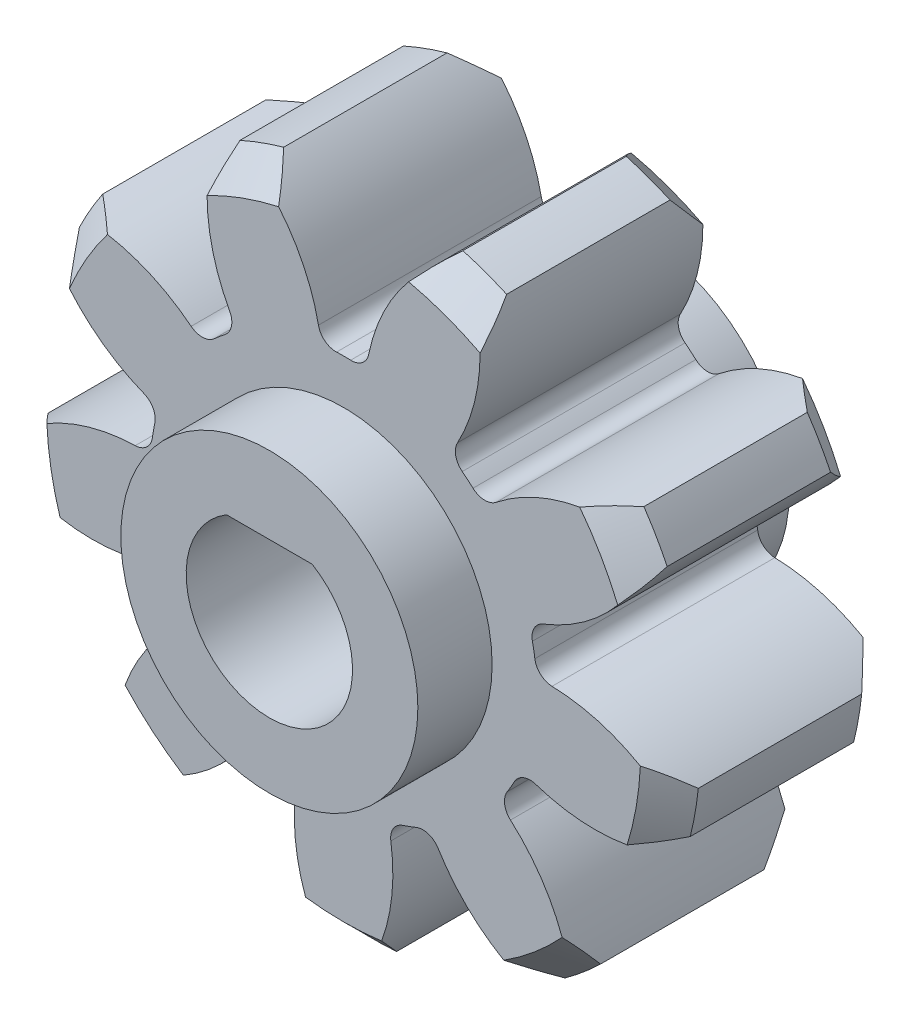
SolidWorks part; units mm, degrees
ref_plane "Přední rovina" through (0, 0, 0) normal (0, 0, 1) x (1, 0, 0)
ref_plane "Horní rovina" through (0, 0, 0) normal (0, 1, 0) x (1, 0, 0)
ref_plane "Pravá rovina" through (0, 0, 0) normal (1, 0, 0) x (0, 0, -1)
sketch "Skica1" plane through (0, 0, 0) normal (0, 0, 1) x (1, 0, 0)
  circle A0 centre (0, 0) radius 11
  circle A1 centre (0, 0) radius 9 construction
  dimension "D1" = 22
  dimension "D2" = 18
extrude "Přidat vysunutím1" add sketch "Skica1" along normal blind 7.5
sketch "Skica2" plane through (0, 0, 0) normal (0, 0, 1) x (1, 0, 0)
  line L0 (0, 11) -> (0, 0) construction
  line L1 (0, 0) -> (7.0707, 8.4265) construction
  line L2 (3.7622, 10.3366) -> (0, 0) construction
  line L3 (-0.7631, 6.4551) -> (0, 0) construction
  line L4 (-1.5628, 8.8633) -> (1.5628, 8.8633) construction
  line L5 (1.5628, 8.8633) -> (4.5, 7.7942) construction
  line L6 (-2.6145, 10.6848) -> (0, 6.1564) construction
  circle A0 centre (0, 0) radius 7 construction
  circle A2 centre (0, 0) radius 11 construction
  arc A3 (-3.0166, 10.5783) -> (-0.7631, 6.4551) centre (-7.0139, 5.7161) cw
  arc A4 (3.0166, 10.5783) -> (0.7631, 6.4551) centre (7.0139, 5.7161) ccw
  circle A5 centre (0, 0) radius 9 construction
  arc A6 (-3.0166, 10.5783) -> (3.0166, 10.5783) centre (0, 0) cw
  arc A7 (0.7631, 6.4551) -> (-0.7631, 6.4551) centre (0, 0) ccw
  dimension "D3" = 40
  dimension "D4" = 30
  dimension "D1" = 0.5
extrude "Odebrat vysunutím1" cut sketch "Skica2" along normal blind 7.5
fillet "Zaoblit1" radius 0.6 2 edges at (0.7631, 6.4551, 3.75) (-0.7631, 6.4551, 3.75)
chamfer "Zkosení1" distance 1 2 edges at (0, -11, 0) (0, -11, 7.5)
pattern_circular "Kruhové pole1" count 9 every 40 about axis through (0, 0, 7.5) along (0, 0, -1) of "Odebrat vysunutím1", "Zaoblit1"
sketch "Skica3" plane through (0, 0, 0) normal (0, 0, 1) x (1, 0, 0)
  circle A0 centre (0, 0) radius 5
  dimension "D1" = 10
extrude "Přidat vysunutím2" add sketch "Skica3" against normal blind 2.5 and the other way blind 10
sketch "Skica5" plane through (0, 0, 10) normal (0, 0, 1) x (1, 0, 0)
  line L0 (-1.4422, 2.4) -> (1.4422, 2.4)
  line L1 (0, -3.3491) -> (0, 4.293) construction
  arc A0 (-1.4422, 2.4) -> (1.4422, 2.4) centre (0, 0) ccw
  dimension "D1" = 5.6
  dimension "D2" = 2.4
extrude "Odebrat vysunutím2" cut sketch "Skica5" against normal blind 20
equation "\"Module\"= 2mm"
equation "\"Number of teeth\"= 9"
equation "\"Pressure angle\"= 30"
equation "\"D1@Skica1\"= (\"Number of teeth\" + 2) * \"Module\""
equation "\"D2@Skica1\"= \"Number of teeth\" * \"Module\""
equation "\"D2@Skica2\"= \"Module\" * 2"
equation "\"D3@Skica2\"= 360 / \"Number of teeth\""
equation "\"D4@Skica2\"= \"Pressure angle\""
equation "\"D1@Zaoblit1\"= 0.3 * \"Module\""
equation "\"D1@Kruhové pole1\"= \"Number of teeth\""
equation "\"D2@Kruhové pole1\"= 360 / \"Number of teeth\""
